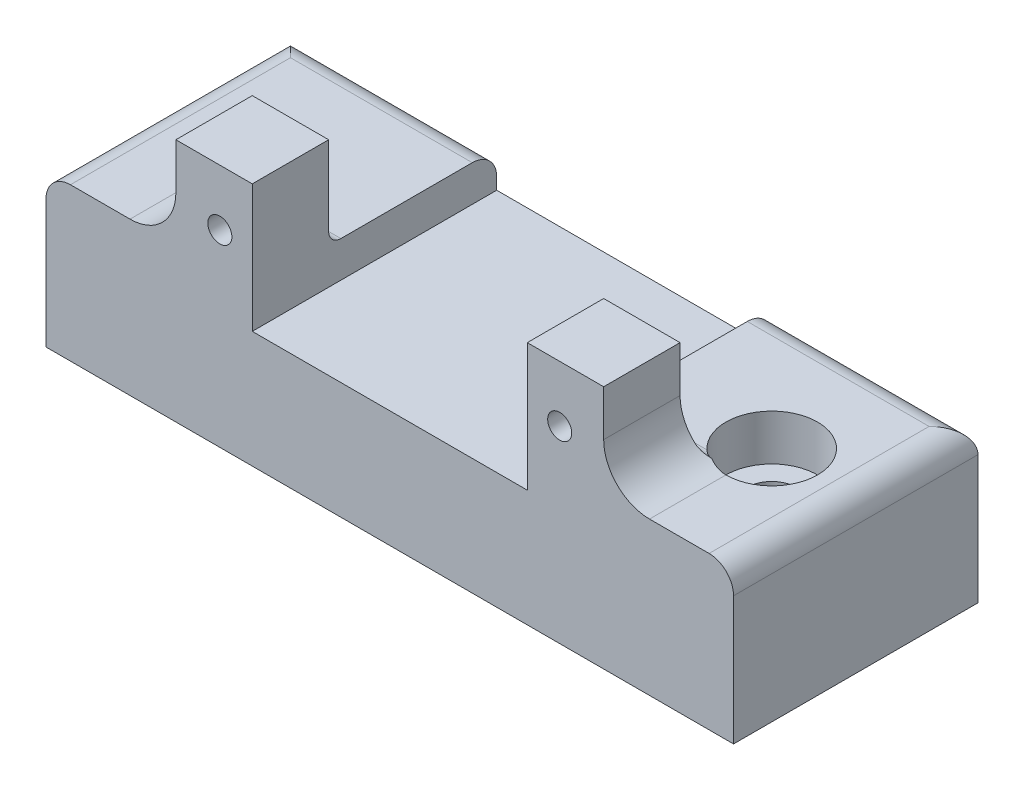
SolidWorks part; units mm, degrees
ref_plane "Front Plane" through (0, 0, 0) normal (0, 0, 1) x (1, 0, 0)
ref_plane "Top Plane" through (0, 0, 0) normal (0, 1, 0) x (1, 0, 0)
ref_plane "Right Plane" through (0, 0, 0) normal (1, 0, 0) x (0, 0, -1)
sketch "Sketch1" plane through (0, 0, 0) normal (0, 1, 0) x (1, 0, 0)
  line L1 (-28.575, 10.16) -> (28.575, 10.16)
  line L2 (-28.575, 10.16) -> (-28.575, -10.16)
  line L3 (-28.575, -10.16) -> (28.575, -10.16)
  line L4 (28.575, 10.16) -> (28.575, -10.16)
  point P4 (0, 10.16)
  point P6 (-28.575, 0)
  dimension "D1" = 57.15
  dimension "D2" = 20.32
extrude "Boss-Extrude1" add sketch "Sketch1" along normal blind 12.7
sketch "Sketch2" plane through (0, 12.7, 0) normal (0, 1, 0) x (1, 0, 0)
  line L0 (-11.43, -6.985) -> (11.43, -6.985) construction
  line L5 (-28.575, -10.16) -> (28.575, -10.16) construction
  line L6 (-11.43, -3.81) -> (-17.78, -3.81)
  line L7 (-11.43, -3.81) -> (-11.43, -10.16)
  line L8 (-11.43, -10.16) -> (-17.78, -10.16)
  line L9 (-17.78, -3.81) -> (-17.78, -10.16)
  line L10 (0, -55) -> (0, 55) construction
  line L11 (11.43, -10.16) -> (17.78, -10.16)
  line L12 (17.78, -3.81) -> (17.78, -10.16)
  line L13 (11.43, -3.81) -> (17.78, -3.81)
  line L14 (11.43, -3.81) -> (11.43, -10.16)
  point P2 (0, -6.985)
  dimension "D1" = 22.86
  dimension "D3" = 6.35
  dimension "D4" = 6.35
extrude "Boss-Extrude2" add sketch "Sketch2" along normal blind 7.62
hole_wizard "CBORE for #3 Binding Head Machine Screw1" positions "Sketch3" profile "Sketch5" counterbore size "#3" standard "ANSI Inch" end condition through all
sketch "Sketch3" plane through (0, 12.7, 0) normal (0, 1, 0) x (1, 0, 0)
  line L1 (-21.59, 0) -> (21.59, 0) construction
  line L3 (0, -6.985) -> (0, 6.985) construction
  line L4 (-6.985, 0) -> (6.985, 0) construction
  point P0 (-21.59, 0)
  point P2 (21.59, 0)
  point P12 (0, 0)
  dimension "D1" = 43.18
sketch "Sketch5" plane through (-21.59, 12.7, 0) normal (1, 0, 0) x (0, 0, 1)
  line L0 (0, 0) -> (0, 12.7)
  line L1 (0, 12.7) -> (2.032, 12.7)
  line L3 (2.032, 12.7) -> (2.032, 3.81)
  line L4 (2.032, 3.81) -> (3.81, 3.81)
  line L5 (3.81, 3.81) -> (3.81, 0)
  line L7 (3.81, 0) -> (0, 0)
  line L11 (0, -6.35) -> (0, 107.95) construction
  dimension "Thru Hole Dia." = 4.064
  dimension "Thru Hole Depth" = 12.7
  dimension "C'Bore Dia." = 7.62
  dimension "C'Bore Depth" = 3.81
hole_wizard "Ø2.0 (2) Diameter Hole1" positions "Sketch8" profile "Sketch9" hole size "Ø2.0" standard "ANSI Metric" end condition through all
sketch "Sketch8" plane through (0, 0, 10.16) normal (0, 0, 1) x (1, 0, 0)
  line L0 (-14.125, 15.65) -> (14.125, 15.65) construction
  line L2 (0, -11.176) -> (0, 11.176) construction
  line L4 (-11.43, 12.7) -> (11.43, 12.7) construction
  point P0 (-14.125, 15.65)
  point P2 (14.125, 15.65)
  point P9 (0, 15.65)
  dimension "D1" = 28.25
  dimension "D2" = 2.95
sketch "Sketch9" plane through (-14.125, 15.65, 10.16) normal (1, 0, 0) x (0, -1, 0)
  line L0 (0, 0) -> (0, 20.32)
  line L1 (0, 20.32) -> (1, 20.32)
  line L2 (1, 20.32) -> (1, 0)
  line L5 (1, 0) -> (0, 0)
  line L11 (0, -6.35) -> (0, 107.95) construction
  dimension "Thru Hole Dia." = 2
  dimension "Thru Hole Depth" = 20.32
sketch "Sketch10" plane through (0, 0, 10.16) normal (0, 0, 1) x (1, 0, 0)
  line L0 (11.43, 20.32) -> (11.43, 12.7) construction
  line L1 (-11.43, 12.7) -> (11.43, 12.7)
  line L2 (-11.43, 12.7) -> (-11.43, 9.7)
  line L3 (-11.43, 9.7) -> (11.43, 9.7)
  line L4 (11.43, 12.7) -> (11.43, 9.7)
  dimension "D1" = 3
extrude "Cut-Extrude1" cut sketch "Sketch10" against normal up to next
fillet "Fillet1" radius 3.81 2 edges at (17.78, 12.7, 6.985) (-17.78, 12.7, 6.985)
fillet "Fillet2" radius 2.032 4 edges at (-20.0025, 12.7, -10.16) (20.0025, 12.7, -10.16) (28.575, 12.7, 0) (-28.575, 12.7, 0)
fillet "Fillet3" radius 1.016 2 edges at (16.51, 12.7, 3.81) (-16.51, 12.7, 3.81)
